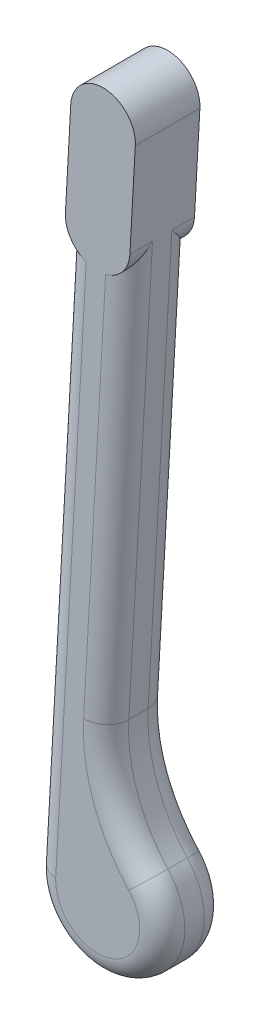
SolidWorks part; units mm, degrees
ref_plane "前视基准面" through (0, 0, 0) normal (0, 0, 1) x (1, 0, 0)
ref_plane "上视基准面" through (0, 0, 0) normal (0, 1, 0) x (1, 0, 0)
ref_plane "右视基准面" through (0, 0, 0) normal (1, 0, 0) x (0, 0, -1)
sketch "草图1" plane through (0, 0, 0) normal (0, 0, 1) x (1, 0, 0)
  line L2 (-9.9846, 0.5556) -> (-19.9691, -178.8889)
  line L3 (9.9846, -0.5556) -> (2.6417, -132.5229)
  arc A1 (2.6417, -132.5229) -> (14.7599, -166.5039) centre (49.0961, -135.1077) ccw
  arc A4 (-19.9691, -178.8889) -> (14.7599, -166.5039) centre (0, -180) ccw
  arc A5 (-9.9846, 0.5556) -> (9.9846, -0.5556) centre (0, 0) cw
extrude "凸台-拉伸1" add sketch "草图1" along normal blind 20
fillet "圆角1" radius 7 10 edges at (-14.9768, -89.1667, 0) (0.5556, 9.9846, 0) (6.3131, -66.5392, 0) (5.2731, -150.7358, 0) (-14.9768, -89.1667, 20) (0.5556, 9.9846, 20) (6.3131, -66.5392, 20) (5.2731, -150.7358, 20) (6.718, -198.838, 0) (6.718, -198.838, 20)
sketch "草图2" plane through (0, 0, 0) normal (0, 0, 1) x (1, 0, 0)
  line L1 (-9.9846, 0.5556) -> (-8.3179, 30.5092)
  line L4 (11.6512, 29.3981) -> (9.9846, -0.5556)
  arc A2 (-8.3179, 30.5092) -> (11.6512, 29.3981) centre (1.6667, 29.9537) cw
  arc A3 (-9.9846, 0.5556) -> (9.9846, -0.5556) centre (0, 0) ccw
extrude "凸台-拉伸2" add sketch "草图2" along normal blind 20
